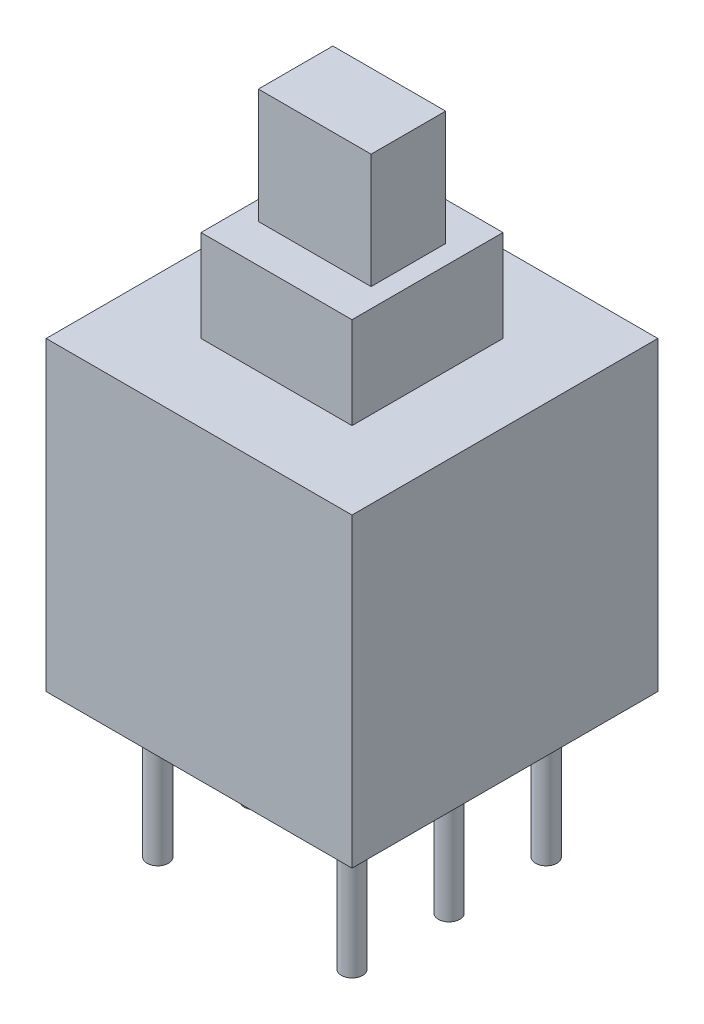
SolidWorks part; units mm, degrees
ref_plane "Front Plane" through (0, 0, 0) normal (0, 0, 1) x (1, 0, 0)
ref_plane "Top Plane" through (0, 0, 0) normal (0, 1, 0) x (1, 0, 0)
ref_plane "Right Plane" through (0, 0, 0) normal (1, 0, 0) x (0, 0, -1)
sketch "Sketch1" plane through (0, 0, 0) normal (0, 1, 0) x (1, 0, 0)
  line L1 (-4, -4) -> (4, -4)
  line L2 (-4, -4) -> (-4, 4)
  line L3 (-4, 4) -> (4, 4)
  line L4 (4, -4) -> (4, 4)
  line L5 (-4, -4) -> (4, 4) construction
  line L6 (-4, 4) -> (4, -4) construction
  point P0 (0, 0)
  dimension "D1" = 8
extrude "Boss-Extrude1" add sketch "Sketch1" along normal blind 8 contours L3 L4 L1 L2
sketch "Sketch2" plane through (0, 8, 0) normal (0, 1, 0) x (1, 0, 0)
  line L1 (-1.975, -1.975) -> (1.975, -1.975)
  line L2 (-1.975, -1.975) -> (-1.975, 1.975)
  line L3 (-1.975, 1.975) -> (1.975, 1.975)
  line L4 (1.975, -1.975) -> (1.975, 1.975)
  line L5 (-1.975, -1.975) -> (1.975, 1.975) construction
  line L6 (-1.975, 1.975) -> (1.975, -1.975) construction
  point P0 (0, 0)
  dimension "D1" = 3.95
extrude "Boss-Extrude2" add sketch "Sketch2" along normal blind 2.4 contours L3 L4 L1 L2
sketch "Sketch3" plane through (0, 10.4, 0) normal (0, 1, 0) x (1, 0, 0)
  line L1 (-1.475, -0.975) -> (1.475, -0.975)
  line L2 (-1.475, -0.975) -> (-1.475, 0.975)
  line L3 (-1.475, 0.975) -> (1.475, 0.975)
  line L4 (1.475, -0.975) -> (1.475, 0.975)
  line L5 (-1.475, -0.975) -> (1.475, 0.975) construction
  line L6 (-1.475, 0.975) -> (1.475, -0.975) construction
  point P0 (0, 0)
  dimension "D1" = 2.95
  dimension "D2" = 1.95
extrude "Boss-Extrude3" add sketch "Sketch3" along normal blind 3 contours L3 L4 L1 L2
sketch "Sketch4" plane through (0, 0, 0) normal (0, -1, 0) x (1, 0, 0)
  line L0 (2.54, 2.54) -> (2.54, 0) construction
  line L1 (2.54, 0) -> (2.54, -2.54) construction
  line L2 (-2.54, 0) -> (2.54, 0) construction
  line L3 (-2.54, -2.54) -> (-2.54, 0) construction
  line L4 (-2.54, 0) -> (-2.54, 2.54) construction
  circle A0 centre (2.54, 2.54) radius 0.28
  circle A1 centre (2.54, 0) radius 0.28
  circle A2 centre (2.54, -2.54) radius 0.28
  circle A3 centre (-2.54, -2.54) radius 0.28
  circle A4 centre (-2.54, 0) radius 0.28
  circle A5 centre (-2.54, 2.54) radius 0.28
  point P8 (2.5018, 2.9409)
  point P13 (-2.3022, 3.0374)
  point P14 (-2.3013, -0.0276)
  dimension "D3" = 0.56
  dimension "D1" = 2.54
  dimension "D2" = 5.08
extrude "Boss-Extrude4" add sketch "Sketch4" along normal blind 3.75
